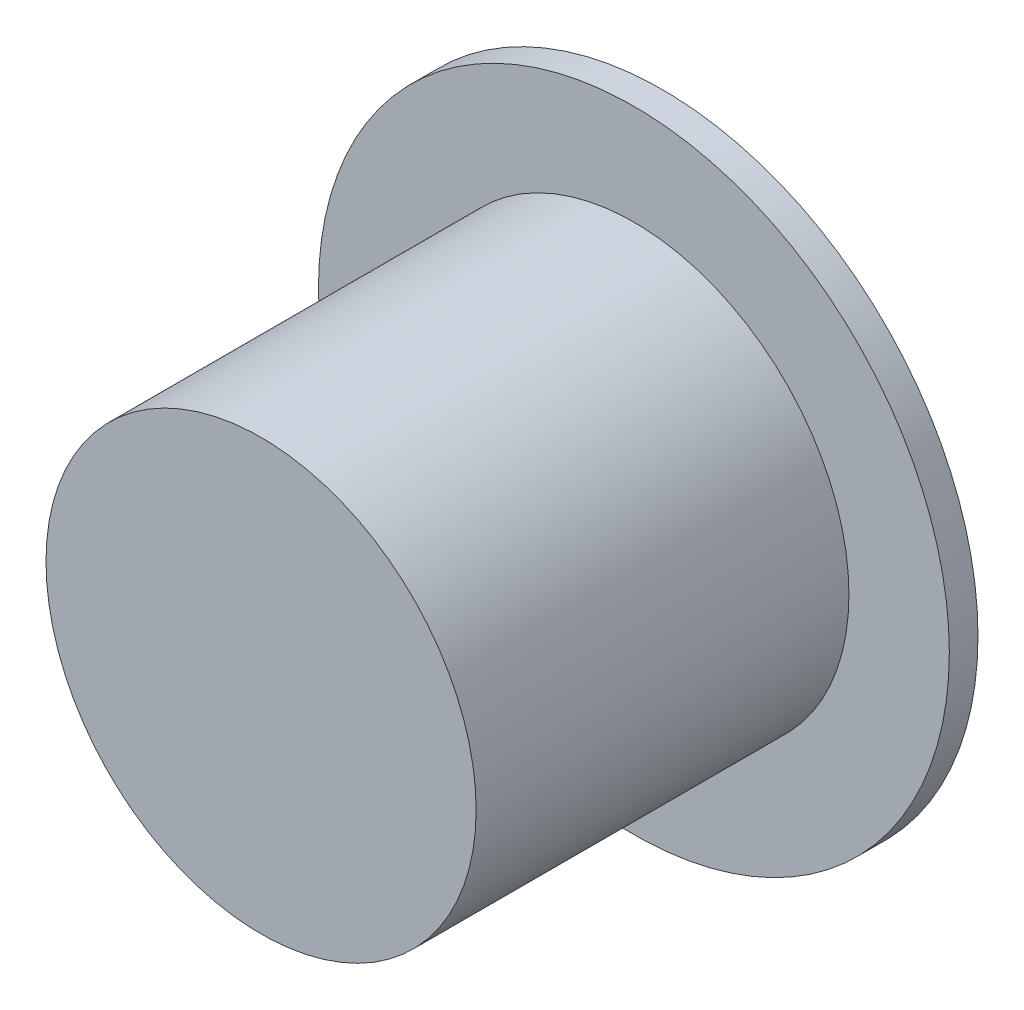
SolidWorks part; units mm, degrees
ref_plane "Front Plane" through (0, 0, 0) normal (0, 0, 1) x (1, 0, 0)
ref_plane "Top Plane" through (0, 0, 0) normal (0, 1, 0) x (1, 0, 0)
ref_plane "Right Plane" through (0, 0, 0) normal (1, 0, 0) x (0, 0, -1)
sketch "Sketch1" plane through (0, 0, 0) normal (0, 0, 1) x (1, 0, 0)
  line L1 (-3.425, -3.425) -> (3.425, -3.425)
  line L2 (-3.425, -3.425) -> (-3.425, 3.425)
  line L3 (-3.425, 3.425) -> (3.425, 3.425)
  line L4 (3.425, -3.425) -> (3.425, 3.425)
  line L5 (-3.425, -3.425) -> (3.425, 3.425) construction
  line L6 (-3.425, 3.425) -> (3.425, -3.425) construction
  circle A0 centre (0, 0) radius 7.5
  point P0 (0, 0)
  point P9 (0, 0)
  dimension "D2" = 15
  dimension "D1" = 6.85
extrude "Boss-Extrude1" add sketch "Sketch1" along normal mid plane 12
ref_axis "Axis1" through (0, 0, 0) along (0, 0, 1)
sketch "Sketch2" plane through (0, 0, -6) normal (0, 0, -1) x (-1, 0, 0)
  circle A0 centre (0, 0) radius 11
  circle A1 centre (0, 0) radius 7.5
  circle A2 centre (0, 0) radius 7.5 construction
  dimension "D1" = 3.5
extrude "Boss-Extrude2" add sketch "Sketch2" against normal blind 1
extrude "Boss-Extrude3" add sketch "Sketch1<2>" along normal blind 2 from surface contours L1 L4 L3 L2 | A0 L4 L1 L2 L3 region at (0, 0, 0) region at (-7.2879, 0, 0) starting at face at (7.5, 0, 6)
sketch "Sketch1<2>" plane through (0, 0, 0) normal (0, 0, 1) x (1, 0, 0) same geometry as "Sketch1"
